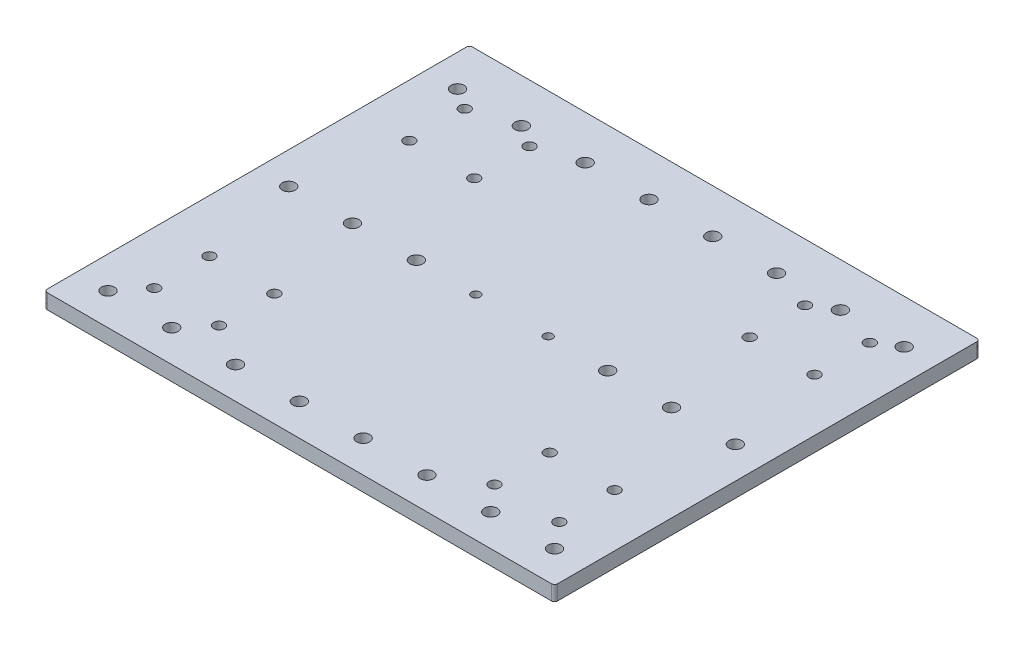
SolidWorks part; units mm, degrees
ref_plane "Front Plane" through (0, 0, 0) normal (0, 0, 1) x (1, 0, 0)
ref_plane "Top Plane" through (0, 0, 0) normal (0, 1, 0) x (1, 0, 0)
ref_plane "Right Plane" through (0, 0, 0) normal (1, 0, 0) x (0, 0, -1)
sketch "Sketch1" plane through (0, 0, 0) normal (0, 1, 0) x (1, 0, 0)
  line L1 (-120, -100) -> (120, -100)
  line L2 (-120, -100) -> (-120, 100)
  line L3 (-120, 100) -> (120, 100)
  line L4 (120, -100) -> (120, 100)
  line L5 (-120, -100) -> (120, 100) construction
  line L6 (-120, 100) -> (120, -100) construction
  point P0 (0, 0)
  dimension "D1" = 240
  dimension "D2" = 200
extrude "Boss-Extrude1" add sketch "Sketch1" along normal mid plane 7
sketch "Sketch2" plane through (0, 3.5, 0) normal (0, 1, 0) x (1, 0, 0)
  line L5 (-80, 100) -> (-80, -100)
  line L6 (-80, 100) -> (-80, -100) construction
  line L8 (80, -100) -> (80, 100)
  line L9 (80, -100) -> (80, 100) construction
  line L11 (120, 60) -> (-120, 60)
  line L12 (120, 60) -> (-120, 60) construction
  line L14 (-120, -60) -> (120, -60)
  line L15 (-120, -60) -> (120, -60) construction
  line L16 (-95.25, 73) -> (-64.75, 73) construction
  line L17 (-95.25, 73) -> (-95.25, 47) construction
  line L18 (-95.25, 47) -> (-64.75, 47) construction
  line L19 (-64.75, 73) -> (-64.75, 47) construction
  line L20 (-95.25, 73) -> (-64.75, 47) construction
  line L21 (-95.25, 47) -> (-64.75, 73) construction
  line L22 (64.75, 47) -> (95.25, 47) construction
  line L23 (64.75, 47) -> (64.75, 73) construction
  line L24 (64.75, 73) -> (95.25, 73) construction
  line L25 (95.25, 47) -> (95.25, 73) construction
  line L26 (64.75, 47) -> (95.25, 73) construction
  line L27 (64.75, 73) -> (95.25, 47) construction
  line L28 (64.75, -47) -> (95.25, -47) construction
  line L29 (64.75, -47) -> (64.75, -73) construction
  line L30 (64.75, -73) -> (95.25, -73) construction
  line L31 (95.25, -47) -> (95.25, -73) construction
  line L32 (64.75, -47) -> (95.25, -73) construction
  line L33 (64.75, -73) -> (95.25, -47) construction
  line L34 (-95.25, -73) -> (-64.75, -73) construction
  line L35 (-95.25, -73) -> (-95.25, -47) construction
  line L36 (-95.25, -47) -> (-64.75, -47) construction
  line L37 (-64.75, -73) -> (-64.75, -47) construction
  line L38 (-95.25, -73) -> (-64.75, -47) construction
  line L39 (-95.25, -47) -> (-64.75, -73) construction
  circle A0 centre (-95.25, 73) radius 2.55
  circle A1 centre (-95.25, 47) radius 2.55
  circle A2 centre (-64.75, 73) radius 2.55
  circle A3 centre (-64.75, 47) radius 2.55
  circle A4 centre (-95.25, -47) radius 2.55
  circle A5 centre (-95.25, -73) radius 2.55
  circle A6 centre (-64.75, -73) radius 2.55
  circle A7 centre (-64.75, -47) radius 2.55
  circle A8 centre (95.25, -47) radius 2.55
  circle A9 centre (64.75, -47) radius 2.55
  circle A10 centre (64.75, -73) radius 2.55
  circle A11 centre (95.25, -73) radius 2.55
  circle A12 centre (64.75, 73) radius 2.55
  circle A13 centre (64.75, 47) radius 2.55
  circle A14 centre (95.25, 73) radius 2.55
  circle A15 centre (95.25, 47) radius 2.55
  point P0 (-80, 60)
  point P13 (80, 60)
  point P18 (80, -60)
  point P23 (-80, -60)
  dimension "D13" = 5.1
  dimension "D14" = 5.1
  dimension "D15" = 5.1
  dimension "D16" = 5.1
  dimension "D17" = 5.1
  dimension "D18" = 5.1
  dimension "D19" = 5.1
  dimension "D20" = 5.1
  dimension "D21" = 5.1
  dimension "D22" = 5.1
  dimension "D23" = 5.1
  dimension "D24" = 5.1
  dimension "D25" = 5.1
  dimension "D26" = 5.1
  dimension "D27" = 5.1
  dimension "D28" = 5.1
  dimension "D1" = 40
  dimension "D5" = 30.5
  dimension "D6" = 26
  dimension "D7" = 30.5
  dimension "D8" = 26
  dimension "D9" = 26
  dimension "D10" = 30.5
  dimension "D11" = 26
  dimension "D12" = 30.5
  dimension "D2" = 40
  dimension "D3" = 40
  dimension "D4" = 40
extrude "Cut-Extrude1" cut sketch "Sketch2" against normal through all
sketch "Sketch3" plane through (0, 3.5, 0) normal (0, 1, 0) x (1, 0, 0)
  line L3 (-17, 0) -> (17, 0) construction
  circle A0 centre (-17, 0) radius 2.05
  circle A1 centre (17, 0) radius 2.05
  point P0 (0, 0)
  dimension "D3" = 4.1
  dimension "D4" = 4.1
  dimension "D1" = 34
extrude "Cut-Extrude2" cut sketch "Sketch3" against normal through all
sketch "Sketch4" plane through (0, 3.5, 0) normal (0, 1, 0) x (1, 0, 0)
  line L0 (-105, 100) -> (-105, -100) construction
  line L1 (120, 100) -> (-120, 100) construction
  line L2 (-120, -100) -> (120, -100) construction
  line L3 (-120, 100) -> (-120, -100) construction
  line L4 (-75, 100) -> (-75, -100) construction
  line L5 (-45, 100) -> (-45, -100) construction
  line L6 (-15, 100) -> (-15, -100) construction
  line L7 (15, 100) -> (15, -100) construction
  line L8 (45, 100) -> (45, -100) construction
  line L9 (75, 100) -> (75, -100) construction
  line L10 (105, 100) -> (105, -100) construction
  line L11 (-120, -85) -> (120, -85) construction
  line L12 (-120, 100) -> (-120, -100) construction
  line L13 (120, -100) -> (120, 100) construction
  line L14 (-120, 79.3935) -> (120, 79.3935) construction
  line L15 (-120, 0) -> (120, 0) construction
  circle A0 centre (-105, 79.3935) radius 3.05
  circle A1 centre (-75, 79.3935) radius 3.05
  circle A2 centre (-45, 79.3935) radius 3.05
  circle A3 centre (-15, 79.3935) radius 3.05
  circle A4 centre (15, 79.3935) radius 3.05
  circle A5 centre (45, 79.3935) radius 3.05
  circle A6 centre (75, 79.3935) radius 3.05
  circle A7 centre (105, 79.3935) radius 3.05
  circle A8 centre (-105, 0) radius 3.05
  circle A9 centre (-105, -85) radius 3.05
  circle A10 centre (-75, 0) radius 3.05
  circle A11 centre (-45, 0) radius 3.05
  circle A14 centre (45, 0) radius 3.05
  circle A15 centre (75, 0) radius 3.05
  circle A16 centre (105, 0) radius 3.05
  circle A17 centre (-75, -85) radius 3.05
  circle A18 centre (-45, -85) radius 3.05
  circle A19 centre (-15, -85) radius 3.05
  circle A20 centre (15, -85) radius 3.05
  circle A21 centre (45, -85) radius 3.05
  circle A22 centre (75, -85) radius 3.05
  circle A23 centre (105, -85) radius 3.05
  circle A24 centre (-15, 0) radius 3.05 [skipped]
  circle A25 centre (15, 0) radius 3.05 [skipped]
  point P6 (-120, 0)
  dimension "D3" = 6.1
  dimension "D4" = 6.1
  dimension "D5" = 6.1
  dimension "D1" = 15
  dimension "D2" = 15
  dimension "D6" = 8
extrude "Cut-Extrude3" cut sketch "Sketch4" against normal through all
fillet "Fillet1" radius 1.5 4 edges at (-120, 0, -100) (120, 0, -100) (-120, 0, 100) (120, 0, 100)
equation "\"D4@Sketch4\"=\"D3@Sketch4\""
equation "\"D5@Sketch4\"=\"D3@Sketch4\""
